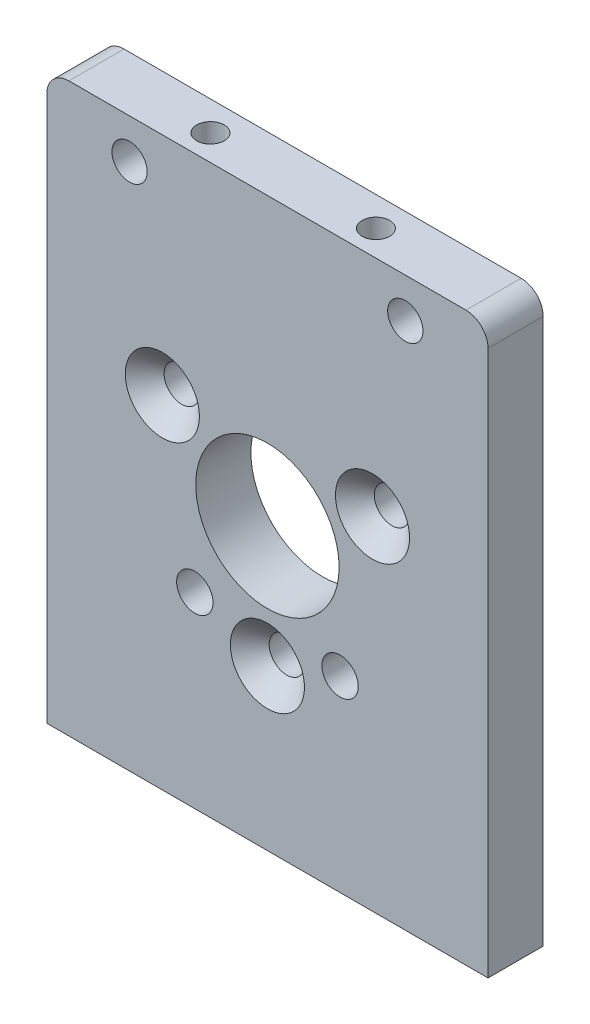
SolidWorks part; units mm, degrees
note: '?' marks a value the reader was unsure of.
material "Plain Carbon Steel"
ref_plane "Front Plane" through (0, 0, 0) normal (0, 0, 1) x (1, 0, 0)
ref_plane "Top Plane" through (0, 0, 0) normal (0, 1, 0) x (1, 0, 0)
ref_plane "Right Plane" through (0, 0, 0) normal (1, 0, 0) x (0, 0, -1)
sketch "Sketch1" plane through (0, 0, 0) normal (0, 0, 1) x (1, 0, 0)
  line L0 (-20, 51.4408) -> (-20, 0)
  line L1 (-20, 51.4408) -> (20, 51.4408)
  line L2 (-20, 0) -> (20, 0)
  line L3 (20, 51.4408) -> (20, 0)
  line L4 (0, 0) -> (0, 51.4408) construction
  line L5 (0, 25.5) -> (-9.5263, 31) construction
  line L6 (-14, 51.4408) -> (-14, 0) construction
  line L7 (14, 51.4408) -> (14, 0) construction
  line L8 (-20, 47.8408) -> (-12.5, 47.8408) construction
  line L9 (-12.5, 47.8408) -> (-14, 47.8408) construction
  line L10 (-12.5, 47.8408) -> (-12.5, 51.4408) construction
  line L11 (-12.5, 47.8408) -> (-11.2305, 45.5718) construction
  line L12 (-11.2305, 45.5718) -> (0, 25.5) construction
  line L13 (-6.5812, 0) -> (-6.5812, 17) construction
  line L14 (-6.5812, 17) -> (0, 25.5) construction
  line L15 (20, 25.5) -> (-20, 25.5) construction
  line L16 (-6.5812, 17) -> (0, 17) construction
  line L17 (0, 17) -> (6.5812, 17) construction
  line L18 (6.5812, 17) -> (0, 25.5) construction
  circle A0 centre (0, 25.5) radius 6.5
  circle A1 centre (0, 25.5) radius 11 construction
  circle A2 centre (0, 14.5) radius 1.6
  circle A3 centre (-9.5263, 31) radius 1.6
  circle A4 centre (9.5263, 31) radius 1.6
  circle A5 centre (-12.5, 47.8408) radius 1.6
  circle A6 centre (-12.5, 47.8408) radius 2.6 construction
  circle A7 centre (12.5, 47.8408) radius 2.6 construction
  circle A8 centre (12.5, 47.8408) radius 1.6
  circle A9 centre (-6.5812, 17) radius 2 construction
  circle A10 centre (0, 25.5) radius 21.5 construction
  circle A11 centre (6.5812, 17) radius 2 construction
  point P18 (9.5263, 31)
  point P36 (0, 4)
  dimension "D3" = 3.2
  dimension "D7" = 5.2
  dimension "D2" = 13
  dimension "D4" = 22
  dimension "D11" = 43
  dimension "D13" = 4
  dimension "D1" = 40
  dimension "D5" = 120
  dimension "D6" = 28
  dimension "D8" = 23
  dimension "D9" = 10.75
  dimension "D12" = 4
  dimension "D10" = 25
  dimension "D14" = 17
  dimension "D15" = 10.75
  dimension "D16" = 3.6
extrude "Boss-Extrude1" add sketch "Sketch1" along normal blind 5
hole_wizard "M4x0.7 Tapped Hole1" positions "Sketch18" profile "Sketch19" tap size "M4x0.7" standard "ANSI Metric" end condition through all
sketch "Sketch18" plane through (0, 0, 0) normal (0, 0, -1) x (-1, 0, 0)
  point P0 (-6.5812, 17)
  point P3 (6.5812, 17)
sketch "Sketch19" plane through (6.5812, 17, 0) normal (1, 0, 0) x (0, 1, 0)
  line L0 (0, 0) -> (0, 5)
  line L1 (0, 5) -> (1.65, 5)
  line L2 (1.65, 5) -> (1.65, 0)
  line L5 (1.65, 0) -> (0, 0)
  line L11 (0, -6.35) -> (0, 107.95) construction
  dimension "Thru Tap Drill Dia." = 3.3
  dimension "Thru Tap Drill Depth" = 5
cosmetic thread "Hole Thread1" parameters "D2"=4
cosmetic thread "Hole Thread2" parameters "D2"=4
hole_wizard "CSK for M3 SFHCS1" positions "Sketch2" profile "Sketch3" countersink size "M3" standard "ANSI Metric" end condition through all
sketch "Sketch2" plane through (0, 0, 5) normal (0, 0, 1) x (1, 0, 0)
  point P0 (-9.5263, 31)
  point P3 (9.5263, 31)
  point P6 (0, 14.5)
sketch "Sketch3" plane through (-9.5263, 31, 5) normal (1, 0, 0) x (0, -1, 0)
  line L0 (0, 0) -> (0, 5)
  line L1 (0, 5) -> (1.6, 5)
  line L2 (1.6, 5) -> (1.6, 1.76)
  line L3 (1.6, 1.76) -> (3.36, 0)
  line L5 (3.36, 0) -> (0, 0)
  line L6 (-1.6, 1.76) -> (-3.36, 0) construction
  line L11 (0, -6.35) -> (0, 107.95) construction
  dimension "Thru Hole Dia." = 3.2
  dimension "Thru Hole Depth" = 5
  dimension "Near C'Sink Dia." = 6.72
  dimension "Near C'Sink Angle" = 90
fillet "Fillet1" radius 2 2 edges at (-20, 51.4408, 2.5) (20, 51.4408, 2.5)
hole_wizard "M3x0.5 Tapped Hole1" positions "Sketch17" profile "Sketch16" tap size "M3x0.5" standard "ANSI Metric"
sketch "Sketch17" plane through (0, 0, 0) normal (0, -1, 0) x (1, 0, 0)
  line L0 (20, 5) -> (20, 0) construction
  line L1 (-20, 5) -> (-20, 0) construction
  point P0 (-16, 2.5)
  point P2 (16, 2.5)
  point P7 (20, 2.5)
  point P10 (-20, 2.5)
  dimension "D1" = 4
  dimension "D2" = 4
sketch "Sketch16" plane through (-16, 0, 2.5) normal (1, 0, 0) x (0, 0, -1)
  line L0 (0, 0) -> (0, 16.7511)
  line L1 (0, 16.7511) -> (1.25, 16)
  line L2 (1.25, 16) -> (1.25, 0)
  line L5 (1.25, 0) -> (0, 0)
  line L10 (0, 16.7511) -> (-1.25, 16) construction
  line L11 (0, -6.35) -> (0, 107.95) construction
  dimension "Tap Drill Dia." = 2.5
  dimension "Tap Drill Depth" = 16
  dimension "Drill Angle" = 118
cosmetic thread "Hole Thread3" parameters "D1"=12, "D2"=3
cosmetic thread "Hole Thread4" parameters "D1"=12, "D2"=3
hole_wizard "M3 Tapped Hole1" positions "Sketch33" profile "Sketch34" tap size "M3" standard "ISO"
sketch "Sketch33" plane through (0, 51.4408, 0) normal (0, 1, 0) x (1, 0, 0)
  point P0 (7.5, -2.6676)
  dimension "D1" = 7.5
sketch "Sketch34" plane through (7.5, 51.4408, 2.6676) normal (1, 0, 0) x (0, 0, 1)
  line L0 (0, 0) -> (0, 6)
  line L1 (0, 6) -> (1.25, 5.2489)
  line L2 (1.25, 5.2489) -> (1.25, 0)
  line L5 (1.25, 0) -> (0, 0)
  line L10 (0, 6) -> (-1.25, 5.2489) construction
  line L11 (0, -6.35) -> (0, 107.95) construction
  dimension "Tap Drill Dia." = 2.5
  dimension "Tap Drill Depth" = 6
  dimension "Drill Angle" = 118
cosmetic thread "Hole Thread5" parameters "D1"=6, "D2"=3
ref_axis "Mount_Tap (R)" through (16, 16, 2.5) along (0, -1, 0)?
ref_axis "Mount_Tap (L)" through (-16, 16, 2.5) along (0, -1, 0)?
ref_point "AxleCenterL"
ref_point "AxleCenterR"
thread "Thread2" [suppressed] pitch 0.5 start angle 0, offset 0, length 0, pitch 0.5, diameter 3.4
ref_plane "Plane3" through (9.2, 46.4622, 2.6676) normal (0, 0, 1) x (1, 0, 0)
sketch "Thread Profile3" plane through (9.2, 46.4622, 2.6676) normal (0, 0, 1) x (1, 0, 0)
  line L0 (0, 0) -> (0, 0.5) construction
  line L1 (0, 0) -> (0.2706, 0.1562)
  line L2 (0.2706, 0.1562) -> (0.2706, 0.2187)
  line L3 (0.2706, 0.2187) -> (0, 0.375)
  line L4 (0.2706, 0.1875) -> (0, 0.1875) construction
  line L11 (0, 0) -> (0, 0.375)
  point P2 (0, 0)
  dimension "Pitch" = 0.5
  dimension "Profile_Angle" = 60
  dimension "Profile_Land" = 0.0625
  dimension "Profile_Height" = 0.2706
pattern_linear "LPattern1" count 2 spacing 15 along (-1, 0, 0) of "Thread2", "M3 Tapped Hole1"
cosmetic thread "Hole Thread6" parameters "D1"=6, "D2"=3
equation "\"D8@Sketch1\"=(43.2 + 2.8)/2"
equation "\"D16@Sketch1\"=0.5*\"D7@Sketch1\" + 1"
